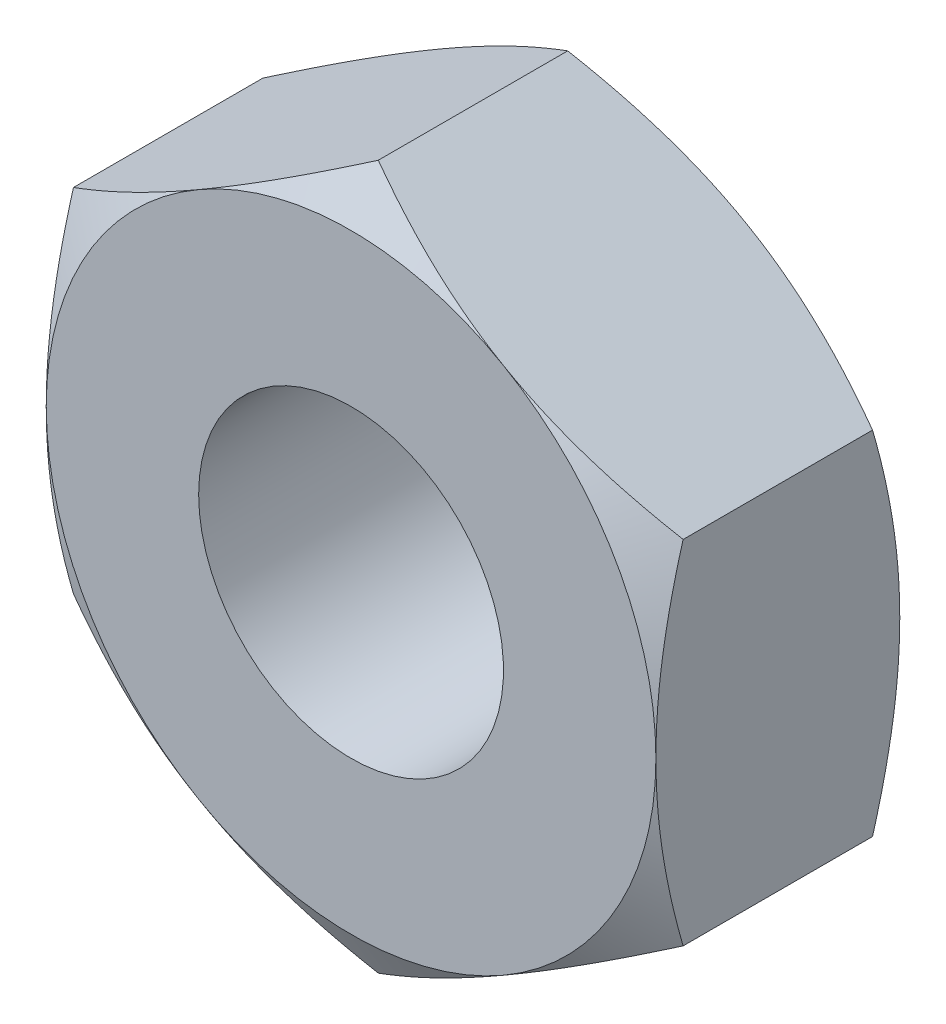
SolidWorks part; units mm, degrees
ref_plane "Front" through (0, 0, 0) normal (0, 0, 1) x (1, 0, 0)
ref_plane "Top" through (0, 0, 0) normal (0, 1, 0) x (1, 0, 0)
ref_plane "Right" through (0, 0, 0) normal (1, 0, 0) x (0, 0, -1)
sketch "Sketch1" plane through (0, 0, 0) normal (0, 0, 1) x (1, 0, 0)
  line L1 (-2, 1.1547) -> (-2, -1.1547)
  line L2 (-2, -1.1547) -> (0, -2.3094)
  line L3 (0, -2.3094) -> (2, -1.1547)
  line L4 (2, -1.1547) -> (2, 1.1547)
  line L5 (2, 1.1547) -> (0, 2.3094)
  line L6 (0, 2.3094) -> (-2, 1.1547)
  circle A0 centre (0, 0) radius 2 construction
  circle A1 centre (0, 0) radius 1 construction
  point P10 (0, 1)
  dimension "hex" = 4
  dimension "dia" = 2
extrude "Extrude1" add sketch "Sketch1" along normal mid plane 1.6
sketch "Sketch4" plane through (0, 0, -0.8) normal (0, 0, -1) x (-1, 0, 0)
  circle A0 centre (0, 0) radius 1 construction
  circle A1 centre (0, 0) radius 1
sketch "Sketch10" plane through (0, 0, 0.8) normal (0, 0, 1) x (1, 0, 0)
  circle A0 centre (0, 0) radius 1 construction
  circle A1 centre (0, 0) radius 1
extrude "Cut-Extrude2" cut sketch "Sketch10" against normal through all draft 45
sketch "Sketch11" plane through (0, 0, -0.8) normal (0, 0, -1) x (-1, 0, 0)
  circle A0 centre (0, 0) radius 1 construction
  circle A1 centre (0, 0) radius 1
extrude "Cut-Extrude3" cut sketch "Sketch11" against normal through all draft 45
sketch "Sketch13" plane through (0, 0, -0.8) normal (0, 0, -1) x (-1, 0, 0)
  circle A0 centre (0, 0) radius 1 construction
  circle A1 centre (0, 0) radius 1
extrude "Boss-Extrude1" add sketch "Sketch13" against normal up to vertex (1.6 mm away) separate body up to point (-2, 1.1547, 0.8)
curve "Helix/Spiral3" [suppressed] pitch 0.4 height 1.6 turns 4
sketch "Sketch12" plane through (0, 0, 0) normal (1, 0, 0) x (0, 0, -1)
  line L0 (1.15, 1) -> (0.8, 1)
  line L1 (1.15, 1) -> (1, 0.7402)
  line L2 (1, 0.7402) -> (0.95, 0.7402)
  line L3 (0.95, 0.7402) -> (0.8, 1)
  line L4 (0.975, 0.7402) -> (0.975, 1) construction
  line L5 (0.875, 0.8701) -> (1.075, 0.8701) construction
  dimension "D1" = 60
  dimension "D2" = 0.05
  dimension "D3" = 0.2
sweep "Cut-Sweep1" [suppressed] cut profiles "Sketch12" path "Helix/Spiral3"
combine bodies "Combine1" operation type subtract main body 116 bodies to subtract 117
sketch "Sketch7" plane through (0, 0, 0.8) normal (0, 0, 1) x (1, 0, 0)
  circle A0 centre (0, 0) radius 2 construction
  circle A1 centre (0, 0) radius 2
extrude "Extrude2" cut sketch "Sketch7" against normal blind 25.4 draft 60 flip side to cut
mirror "Mirror2" about plane through (0, 0, 0) normal (0, 0, 1) of "Extrude2"
sketch "Sketch8" plane through (0, 0, 0.8) normal (0, 0, 1) x (1, 0, 0)
  line L0 (-0.7071, 0.7071) -> (0, 0) construction
  line L1 (0, -1.004) -> (0, 1.004) construction
  circle A1 centre (0, 0) radius 1 construction
  point P0 (-0.7071, 0.7071)
  dimension "D1" = 45
equation "\"D3@Helix/Spiral3\" = \"length@Extrude1\" "
equation "\"D2@Sketch12\" = \"D4@Helix/Spiral3\"*.125"
equation "\"D3@Sketch12\" = \"D4@Helix/Spiral3\"*.50"
